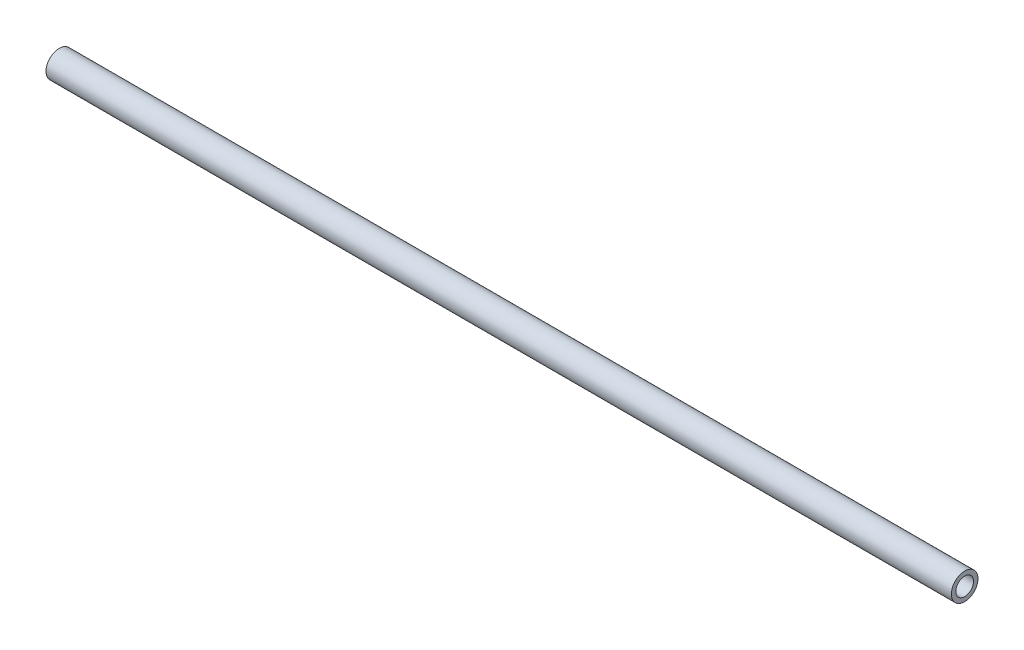
SolidWorks part; units mm, degrees
material "NEOPRENE"
ref_plane "Front Plane" through (0, 0, 0) normal (0, 0, 1) x (1, 0, 0)
ref_plane "Top Plane" through (0, 0, 0) normal (0, 1, 0) x (1, 0, 0)
ref_plane "Right Plane" through (0, 0, 0) normal (1, 0, 0) x (0, 0, -1)
sketch "Sketch1" plane through (0, 0, 0) normal (1, 0, 0) x (0, 0, -1)
  circle A0 centre (0, 0) radius 6.35
  circle A1 centre (0, 0) radius 9.525
  dimension "D1" = 12.7
  dimension "D2" = 19.05
extrude "Boss-Extrude1" add sketch "Sketch1" along normal blind 647.7
